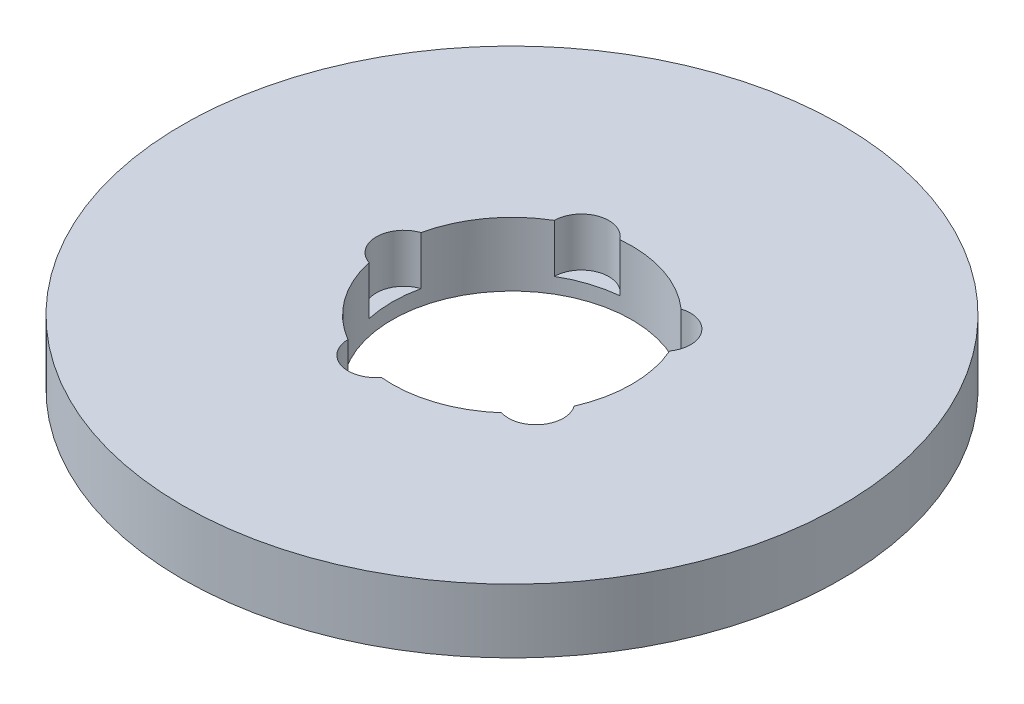
SolidWorks part; units mm, degrees
ref_plane "Front Plane" through (0, 0, 0) normal (0, 0, 1) x (1, 0, 0)
ref_plane "Top Plane" through (0, 0, 0) normal (0, 1, 0) x (1, 0, 0)
ref_plane "Right Plane" through (0, 0, 0) normal (1, 0, 0) x (0, 0, -1)
sketch "Sketch1" plane through (0, 0, 0) normal (0, 1, 0) x (1, 0, 0)
  circle A0 centre (0, 0) radius 82.5
  dimension "FLANGE_OD" = 165
extrude "Boss-Extrude1" add sketch "Sketch1" along normal blind 16
sketch "Sketch2" plane through (0, 0, 0) normal (0, 1, 0) x (1, 0, 0)
  circle A0 centre (0, 0) radius 30
  dimension "BORE_D" = 60
extrude "Cut-Extrude1" cut sketch "Sketch2" along normal through all
sketch "Sketch3" plane through (0, 16, 0) normal (0, 1, 0) x (1, 0, 0)
  circle A0 centre (0, 0) radius 27.0819 construction
  circle A1 centre (-27.0819, 0) radius 6.8724
  dimension "BOLT_D" = 13.7449
  dimension "BOLT_PCD" = 54.1639
extrude "Cut-Extrude2" cut sketch "Sketch3" against normal blind 12.1561
pattern_circular "CirPattern1" count 5 over 360 about axis through (0, 0, 0) along (0, 1, 0) of "Cut-Extrude2"
